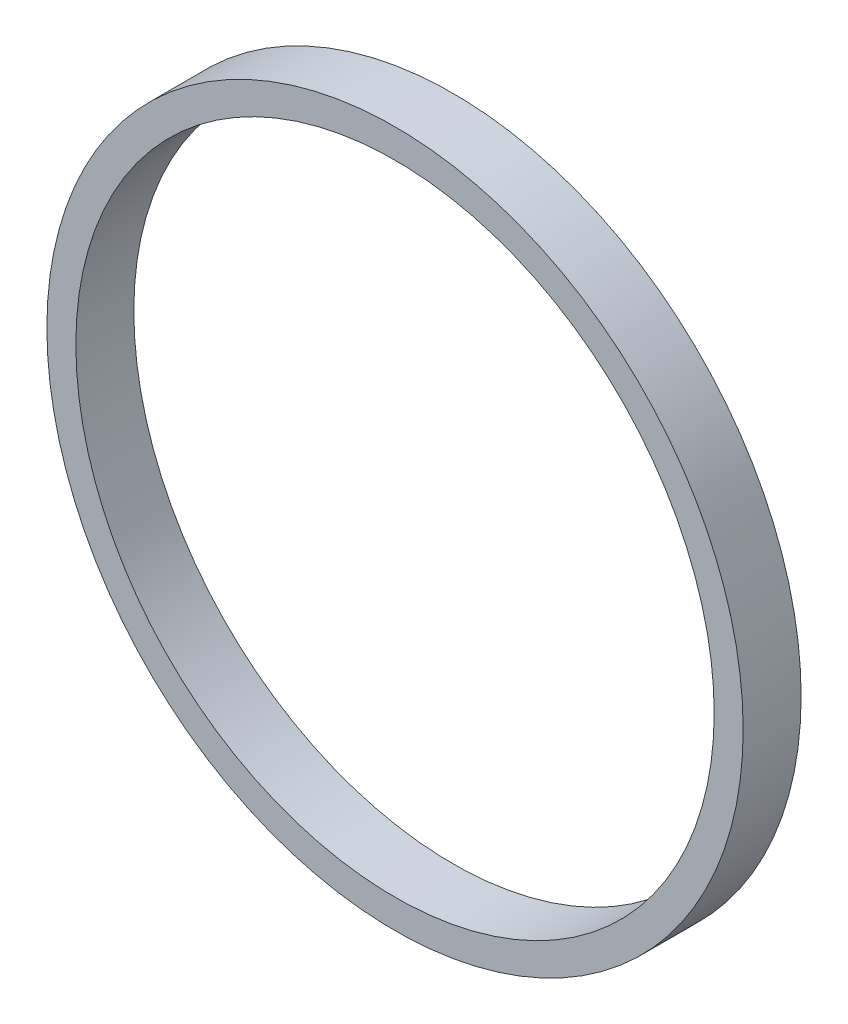
SolidWorks part; units mm, degrees
ref_plane "Front Plane" through (0, 0, 0) normal (0, 0, 1) x (1, 0, 0)
ref_plane "Top Plane" through (0, 0, 0) normal (0, 1, 0) x (1, 0, 0)
ref_plane "Right Plane" through (0, 0, 0) normal (1, 0, 0) x (0, 0, -1)
sketch "Sketch3" plane through (0, 0, 0) normal (0, 0, 1) x (1, 0, 0)
  circle A0 centre (0, 0) radius 24.03
  circle A2 centre (0, 0) radius 22.03
  dimension "D1" = 48.06
  dimension "D2" = 44.06
extrude "Boss-Extrude3" add sketch "Sketch3" along normal blind 4
equation "\"InnerWall\"= 22.03"
equation "\"OuterWall\"= \"InnerWall\" + 2"
equation "\"Depth\"= 4"
equation "\"D1@Sketch3\"=\"OuterWall\"*2"
equation "\"D2@Sketch3\"=\"InnerWall\"*2"
equation "\"D1@Boss-Extrude3\"=\"Depth\""
